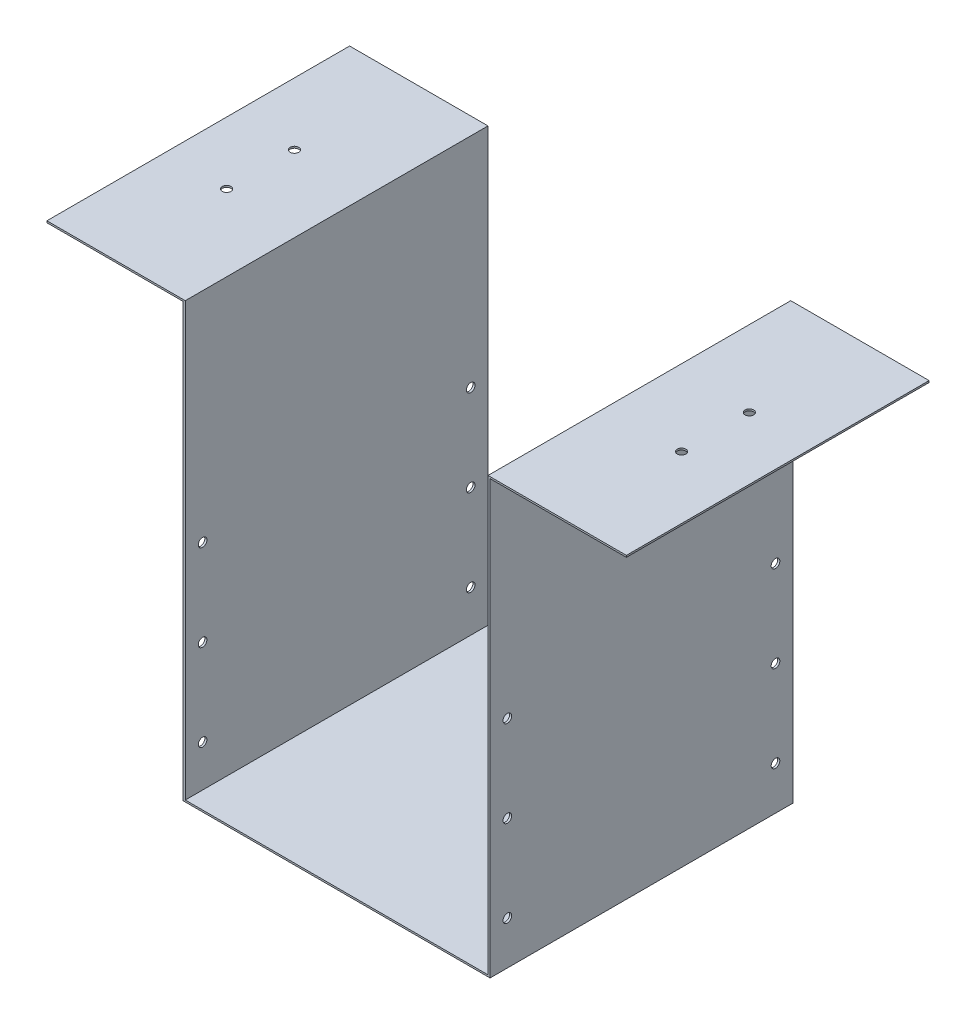
SolidWorks part; units mm, degrees
ref_plane "Front Plane" through (0, 0, 0) normal (0, 0, 1) x (1, 0, 0)
ref_plane "Top Plane" through (0, 0, 0) normal (0, 1, 0) x (1, 0, 0)
ref_plane "Right Plane" through (0, 0, 0) normal (1, 0, 0) x (0, 0, -1)
sketch "Sketch1" plane through (0, 0, 0) normal (0, 1, 0) x (1, 0, 0)
  line L1 (-87.5, -87.5) -> (87.5, -87.5)
  line L2 (-87.5, -87.5) -> (-87.5, 87.5)
  line L3 (-87.5, 87.5) -> (87.5, 87.5)
  line L4 (87.5, -87.5) -> (87.5, 87.5)
  line L5 (-87.5, -87.5) -> (87.5, 87.5) construction
  line L6 (-87.5, 87.5) -> (87.5, -87.5) construction
  point P0 (0, 0)
  dimension "D1" = 175
extrude "Boss-Extrude1" add sketch "Sketch1" along normal blind 1
sketch "Sketch2" plane through (0, 0, 0) normal (0, -1, 0) x (1, 0, 0)
  line L0 (0, -87.5) -> (0, 87.5) construction
  line L1 (-87.5, -87.5) -> (-88.7, -87.5)
  line L2 (-87.5, -87.5) -> (-87.5, 87.5)
  line L3 (-87.5, 87.5) -> (-88.7, 87.5)
  line L4 (-88.7, -87.5) -> (-88.7, 87.5)
  line L5 (87.5, -87.5) -> (-87.5, -87.5) construction
  line L6 (-87.5, 87.5) -> (87.5, 87.5) construction
  line L7 (88.7, -87.5) -> (88.7, 87.5)
  line L8 (87.5, 87.5) -> (88.7, 87.5)
  line L9 (87.5, -87.5) -> (87.5, 87.5)
  line L10 (87.5, -87.5) -> (88.7, -87.5)
  dimension "D1" = 1.2
extrude "Boss-Extrude2" add sketch "Sketch2" against normal blind 250
sketch "Sketch3" plane through (0, 250, 0) normal (0, 1, 0) x (1, 0, 0)
  line L0 (0, 87.5) -> (0, -87.5) construction
  line L1 (-87.5, 87.5) -> (-167.5, 87.5)
  line L2 (-87.5, 87.5) -> (-87.5, -87.5)
  line L3 (-87.5, -87.5) -> (-167.5, -87.5)
  line L4 (-167.5, 87.5) -> (-167.5, -87.5)
  line L5 (87.5, 87.5) -> (-87.5, 87.5) construction
  line L6 (-87.5, -87.5) -> (87.5, -87.5) construction
  line L7 (167.5, 87.5) -> (167.5, -87.5)
  line L8 (87.5, -87.5) -> (167.5, -87.5)
  line L9 (87.5, 87.5) -> (87.5, -87.5)
  line L10 (87.5, 87.5) -> (167.5, 87.5)
  dimension "D1" = 80
extrude "Boss-Extrude3" add sketch "Sketch3" along normal blind 1
sketch "Sketch4" plane through (0, 251, 0) normal (0, 1, 0) x (1, 0, 0)
  line L0 (87.5, 0) -> (131.5, 0) construction
  line L1 (87.5, 0) -> (167.5, 0) construction
  line L2 (131.5, 0) -> (131.5, 19.6) construction
  line L3 (0, 87.5) -> (0, -87.5) construction
  line L4 (87.5, 87.5) -> (-87.5, 87.5) construction
  line L5 (-87.5, -87.5) -> (87.5, -87.5) construction
  line L6 (-131.5, 0) -> (-131.5, 19.6) construction
  line L7 (-87.5, 0) -> (-131.5, 0) construction
  circle A1 centre (131.5, 19.6) radius 2.5
  circle A2 centre (131.5, -19.6) radius 2.5
  circle A3 centre (-131.5, -19.6) radius 2.5
  circle A4 centre (-131.5, 19.6) radius 2.5
  dimension "D3" = 5
  dimension "D1" = 44
  dimension "D2" = 19.6
extrude "Cut-Extrude1" cut sketch "Sketch4" against normal blind 10
sketch "Sketch5" plane through (-88.7, 0, 0) normal (-1, 0, 0) x (0, 0, 1)
  line L0 (-87.5, 207.5) -> (87.5, 207.5) construction
  line L1 (-87.5, 250) -> (-87.5, 0) construction
  line L2 (87.5, 250) -> (87.5, 0) construction
  line L3 (-87.5, 177.5) -> (87.5, 177.5) construction
  line L4 (87.5, 250) -> (-87.5, 250) construction
  dimension "D1" = 42.5
  dimension "D2" = 30
sketch "Sketch6" plane through (88.7, 0, 0) normal (1, 0, 0) x (0, 0, -1)
  line L0 (87.5, 25) -> (77.5, 25) construction
  line L1 (87.5, 250) -> (87.5, 0) construction
  line L2 (87.5, 0) -> (-87.5, 0) construction
  line L3 (0, 0) -> (0, 150.606) construction
  circle A0 centre (77.5, 25) radius 2.5
  circle A1 centre (77.5, 75) radius 2.5
  circle A2 centre (77.5, 125) radius 2.5
  circle A3 centre (-77.5, 125) radius 2.5
  circle A4 centre (-77.5, 75) radius 2.5
  circle A5 centre (-77.5, 25) radius 2.5
  dimension "D2" = 5
  dimension "D1" = 25
  dimension "D4" = 10
  dimension "D3" = 3
extrude "Cut-Extrude2" cut sketch "Sketch6" against normal blind 300
